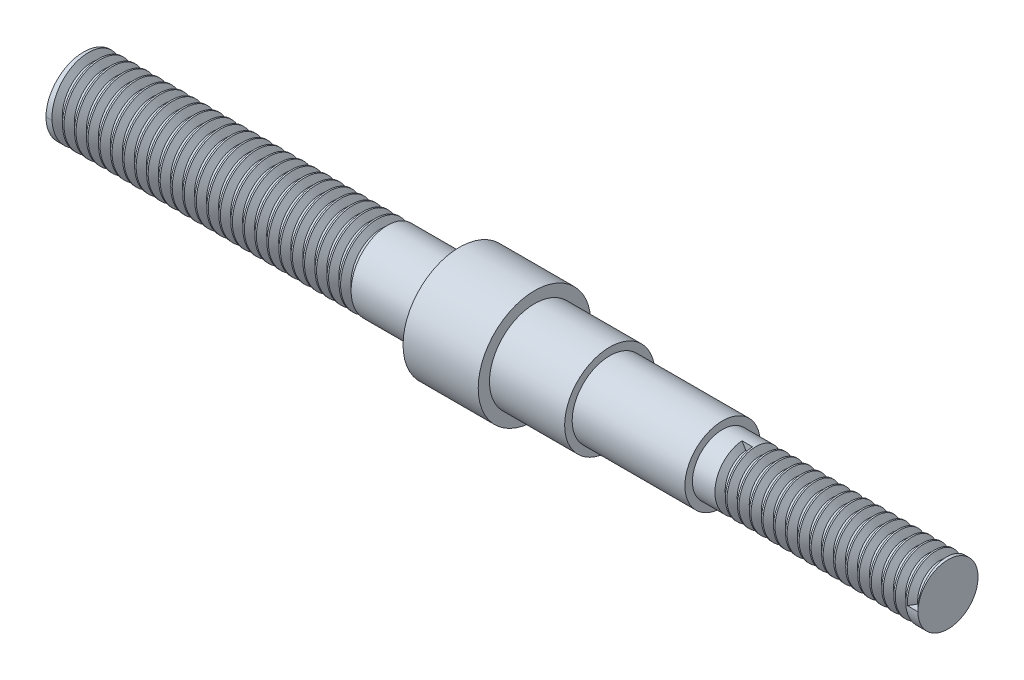
SolidWorks part; units mm, degrees
ref_plane "Front Plane" through (0, 0, 0) normal (0, 0, 1) x (1, 0, 0)
ref_plane "Top Plane" through (0, 0, 0) normal (0, 1, 0) x (1, 0, 0)
ref_plane "Right Plane" through (0, 0, 0) normal (1, 0, 0) x (0, 0, -1)
sketch "Sketch1" plane through (0, 0, 0) normal (0, 0, 1) x (1, 0, 0)
  line L0 (-24.7654, 0) -> (38.6095, 0) construction
  line L1 (-25, 0) -> (-25, 2.5)
  line L2 (-25, 2.5) -> (0, 2.5)
  line L3 (0, 2.5) -> (0, 3.75)
  line L4 (0, 3.75) -> (5, 3.75)
  line L5 (10, 3) -> (10, 2.5)
  line L6 (10, 2.5) -> (17.5, 2.5)
  line L12 (-25, 0) -> (32.5, 0)
  line L14 (17.5, 2.5) -> (17.5, 2)
  line L15 (17.5, 2) -> (32.5, 2)
  line L16 (32.5, 2) -> (32.5, 0)
  line L17 (5, 3.75) -> (5, 3)
  line L18 (5, 3) -> (10, 3)
  dimension "D1" = 25
  dimension "D2" = 5
  dimension "D3" = 7.5
  dimension "D4" = 2.5
  dimension "D5" = 7.5
  dimension "D6" = 5
  dimension "D7" = 5
  dimension "D8" = 6
  dimension "D9" = 4
  dimension "D10" = 15
revolve "Revolve1" add sketch "Sketch1" angle 360 about L0
cosmetic thread "Cosmetic Thread3" parameters "D1"=20, "D2"=4.11
cosmetic thread "Cosmetic Thread4" parameters "D1"=10, "D2"=3.22
thread "Thread1" pitch 0.8 method cut profile "Thread Profile1" start angle 0, offset 0, length 20, pitch 0.8, diameter 5
ref_plane "Plane1" through (-25, 0, -2.5) normal (0, -1, 0) x (0, 0, -1)
sketch "Thread Profile1" plane through (-25, 0, -2.5) normal (0, -1, 0) x (0, 0, -1)
  line L0 (0, 0) -> (0, 0.8) construction
  line L11 (0, 0) -> (0, 0.7)
  line L12 (0, 0.7) -> (-0.433, 0.45)
  line L13 (-0.433, 0.45) -> (-0.433, 0.25)
  line L15 (-0.433, 0.25) -> (0, 0)
  line L17 (-0.433, 0.35) -> (0, 0.35) construction
  point P2 (0, 0)
  dimension "Pitch" = 0.8
  dimension "Profile_Angle" = 60
  dimension "Profile_Land" = 0.2
  dimension "Profile_Height" = 0.433
thread "Thread2" pitch 0.8 method cut profile "Thread Profile2" start angle 0, offset 0, length 13, pitch 0.8, diameter 4
ref_plane "Plane2" through (32.5, 0, 2) normal (0, -1, 0) x (0, 0, 1)
sketch "Thread Profile2" plane through (32.5, 0, 2) normal (0, -1, 0) x (0, 0, 1)
  line L0 (0, 0) -> (0, 0.8) construction
  line L11 (0, 0) -> (0, 0.7)
  line L12 (0, 0.7) -> (-0.433, 0.45)
  line L13 (-0.433, 0.45) -> (-0.433, 0.25)
  line L15 (-0.433, 0.25) -> (0, 0)
  line L17 (-0.433, 0.35) -> (0, 0.35) construction
  point P2 (0, 0)
  dimension "Pitch" = 0.8
  dimension "Profile_Angle" = 60
  dimension "Profile_Land" = 0.2
  dimension "Profile_Height" = 0.433
